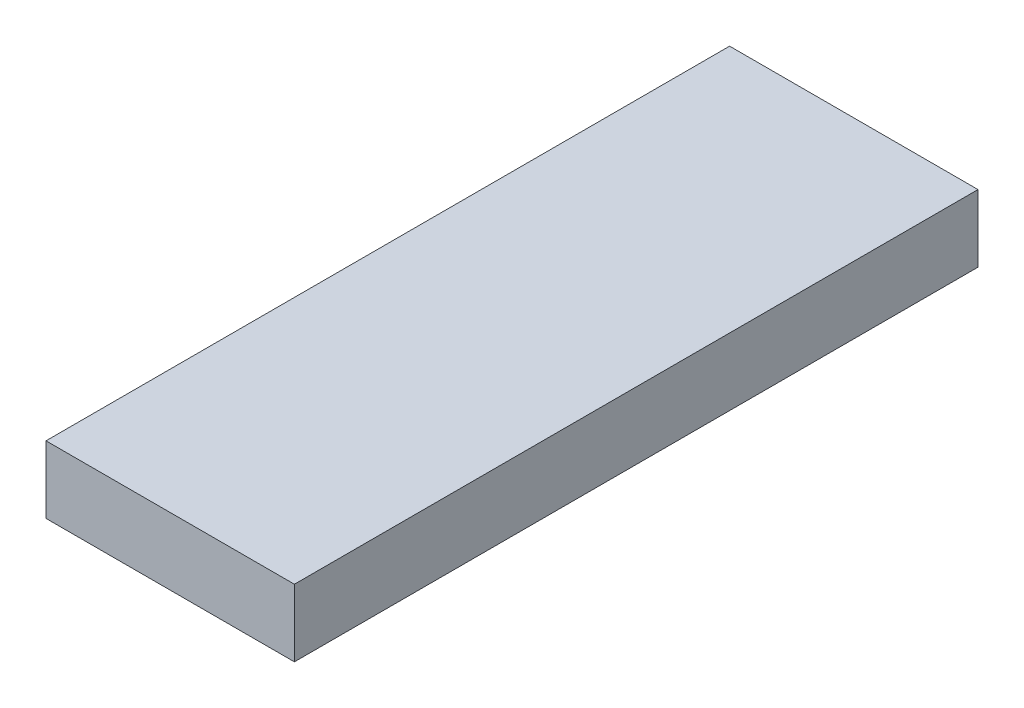
SolidWorks part; units mm, degrees
material "Copper"
ref_plane "Front Plane" through (0, 0, 0) normal (0, 0, 1) x (1, 0, 0)
ref_plane "Top Plane" through (0, 0, 0) normal (0, 1, 0) x (1, 0, 0)
ref_plane "Right Plane" through (0, 0, 0) normal (1, 0, 0) x (0, 0, -1)
sketch "Sketch1" plane through (0, 0, 0) normal (0, 0, 1) x (1, 0, 0)
  line L4 (-5.5416, 52.7251) -> (-5.5416, 55.7251)
  line L5 (26.5078, 45.9128) -> (16.3827, 50.4208)
  line L6 (16.3827, 50.4208) -> (5.5416, 52.7251)
  line L7 (5.5416, 52.7251) -> (-5.5416, 52.7251)
  line L8 (-5.5416, 52.7251) -> (-16.3827, 50.4208)
  line L9 (-16.3827, 50.4208) -> (-26.5078, 45.9128)
  line L10 (-26.5078, 45.9128) -> (-35.4743, 39.3982)
  line L11 (-35.4743, 39.3982) -> (-42.8905, 31.1618)
  line L12 (-42.8905, 31.1618) -> (-48.4321, 21.5634)
  line L13 (-48.4321, 21.5634) -> (-51.857, 11.0226)
  line L14 (-51.857, 11.0226) -> (-53.0156, 0)
  line L15 (-53.0156, 0) -> (-51.857, -11.0226)
  line L16 (-51.857, -11.0226) -> (-48.4321, -21.5634)
  line L17 (-48.4321, -21.5634) -> (-42.8905, -31.1618)
  line L18 (-42.8905, -31.1618) -> (-35.4743, -39.3982)
  line L19 (-35.4743, -39.3982) -> (-26.5078, -45.9128)
  line L20 (-26.5078, -45.9128) -> (-16.3827, -50.4208)
  line L21 (-16.3827, -50.4208) -> (-5.5416, -52.7251)
  line L22 (-5.5416, -52.7251) -> (5.5416, -52.7251)
  line L23 (5.5416, -52.7251) -> (16.3827, -50.4208)
  line L24 (16.3827, -50.4208) -> (26.5078, -45.9128)
  line L25 (26.5078, -45.9128) -> (35.4743, -39.3982)
  line L26 (35.4743, -39.3982) -> (42.8905, -31.1618)
  line L27 (42.8905, -31.1618) -> (48.4321, -21.5634)
  line L28 (48.4321, -21.5634) -> (51.857, -11.0226)
  line L29 (51.857, -11.0226) -> (53.0156, 0)
  line L30 (53.0156, 0) -> (51.857, 11.0226)
  line L31 (51.857, 11.0226) -> (48.4321, 21.5634)
  line L32 (48.4321, 21.5634) -> (42.8905, 31.1618)
  line L33 (42.8905, 31.1618) -> (35.4743, 39.3982)
  line L34 (35.4743, 39.3982) -> (26.5078, 45.9128)
  line L35 (-5.5416, 55.7251) -> (5.5416, 55.7251)
  line L36 (5.5416, 55.7251) -> (5.5416, 52.7251)
  circle A1 centre (0, 0) radius 52.7251 construction
  dimension "D1" = 3
  dimension "D2" = 56
extrude "Boss-Extrude1" add sketch "Sketch1" along normal mid plane 30.5 contours L36 L35 L4 L7 region at (0, 54.2251, 0)
